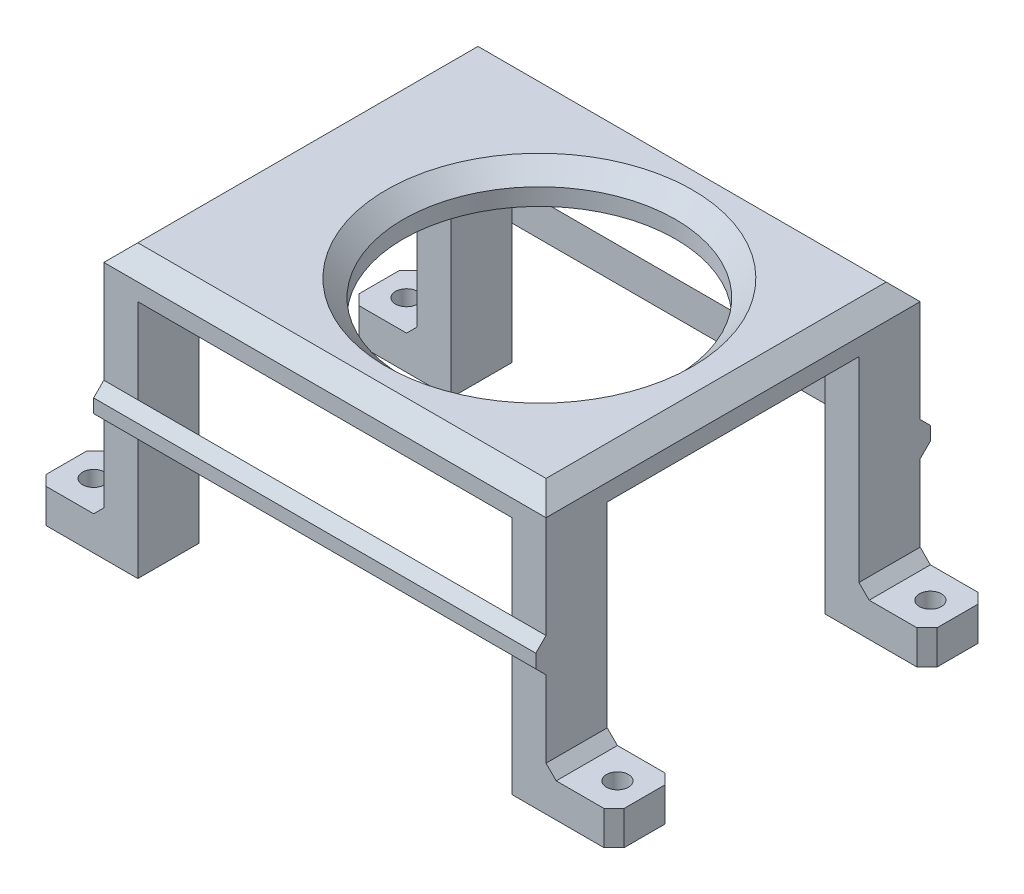
SolidWorks part; units mm, degrees
ref_plane "Front Plane" through (0, 0, 0) normal (0, 0, 1) x (1, 0, 0)
ref_plane "Top Plane" through (0, 0, 0) normal (0, 1, 0) x (1, 0, 0)
ref_plane "Right Plane" through (0, 0, 0) normal (1, 0, 0) x (0, 0, -1)
sketch "Sketch3" plane through (0, 0, 0) normal (0, 0, 1) x (1, 0, 0)
  line L0 (65, 10) -> (85, 10)
  line L2 (55, 0) -> (55, 70.5)
  line L3 (55, 70.5) -> (-55, 70.5)
  line L4 (-55, 0) -> (-55, 70.5)
  line L6 (65, 10) -> (65, 80.5)
  line L7 (65, 80.5) -> (-65, 80.5)
  line L8 (-65, 10) -> (-65, 80.5)
  line L9 (-85, 0) -> (-55, 0)
  line L10 (-85, 0) -> (-85, 10)
  line L11 (-85, 10) -> (-65, 10)
  line L12 (85, 0) -> (85, 10)
  line L14 (55, 0) -> (85, 0)
  point P7 (0, 0)
  point P14 (0, 70.5)
  dimension "D1" = 70.5
  dimension "D2" = 80.5
  dimension "D3" = 10
  dimension "D4" = 10
  dimension "D5" = 10
  dimension "D6" = 30
  dimension "D7" = 30
  dimension "D8" = 110
extrude "Boss-Extrude2" add sketch "Sketch3" along normal blind 110
sketch "Sketch4" plane through (85, 0, 0) normal (1, 0, 0) x (0, 0, -1)
  line L0 (-110, 0) -> (0, 0) construction
  line L1 (-92, 0) -> (-18, 0)
  line L2 (-92, 0) -> (-92, 70.5)
  line L3 (-92, 70.5) -> (-18, 70.5)
  line L4 (-18, 0) -> (-18, 70.5)
  line L6 (0, 0) -> (0, 10) construction
  point P7 (-55, 0)
  point P10 (-55, 0)
  dimension "D1" = 18
  dimension "D2" = 70.5
extrude "Cut-Extrude2" cut sketch "Sketch4" against normal through all contours L2 L1 L4 L3
sketch "Sketch5" plane through (0, 80.5, 0) normal (0, 1, 0) x (1, 0, 0)
  line L2 (55, -110) -> (55, -92) construction
  line L3 (65, -110) -> (65, 0) construction
  circle A0 centre (8.05, -55) radius 40
  point P6 (65, -55)
  dimension "D2" = 80
  dimension "D1" = 46.95
extrude "Cut-Extrude3" cut sketch "Sketch5" against normal up to next
sketch "Sketch6" plane through (0, 10, 0) normal (0, 1, 0) x (1, 0, 0)
  line L1 (85, -110) -> (85, -92) construction
  line L2 (85, -18) -> (85, 0) construction
  line L3 (-85, -18) -> (-85, 0) construction
  circle A0 centre (77, -101) radius 3.25
  circle A1 centre (77, -9) radius 3.25
  circle A2 centre (-77, -9) radius 3.25
  circle A3 centre (-77, -101) radius 3.25
  point P18 (85, -101)
  point P20 (85, -9)
  dimension "D1" = 6.5
  dimension "D3" = 8
  dimension "D2" = 8
extrude "Cut-Extrude4" cut sketch "Sketch6" against normal up to next
sketch "Sketch7" plane through (0, 0, 0) normal (0, 0, -1) x (-1, 0, 0)
  line L0 (-65, 10) -> (-65, 80.5) construction
  line L1 (-65, 45.5) -> (65, 45.5)
  line L2 (-65, 45.5) -> (-65, 35.5)
  line L3 (-65, 35.5) -> (65, 35.5)
  line L4 (65, 45.5) -> (65, 35.5)
  line L5 (65, 80.5) -> (65, 10) construction
  line L6 (55, 70.5) -> (-55, 70.5) construction
  dimension "D1" = 25
  dimension "D2" = 10
extrude "Boss-Extrude3" add sketch "Sketch7" along normal blind 3
ref_plane "Plane1" through (0, 0, 55) normal (0, 0, 1) x (1, 0, 0)
mirror "Mirror1" about plane through (0, 0, 55) normal (0, 0, 1) of "Boss-Extrude3"
chamfer "Chamfer1" distance 3 angle 45 2 edges at (0, 35.5, -3) (0, 45.5, -3)
chamfer "Chamfer2" distance 5 angle 45 5 edges at (-31.95, 80.5, 55) (65, 80.5, 55) (0, 80.5, 110) (-65, 80.5, 55) (0, 80.5, 0)
chamfer "Chamfer3" distance 3 angle 45 2 edges at (0, 35.5, 113) (0, 45.5, 113)
chamfer "Chamfer5" distance 3 angle 45 12 edges at (-65, 10, 9) (-65, 10, 101) (65, 10, 9) (65, 10, 101) (85, 5, 0) (85, 5, 18) (85, 5, 110) (85, 5, 92) (-85, 5, 110) (-85, 5, 92) (-85, 5, 18) (-85, 5, 0)
equation "\"D2@Sketch3\"=\"D1@Sketch3\"+10"
